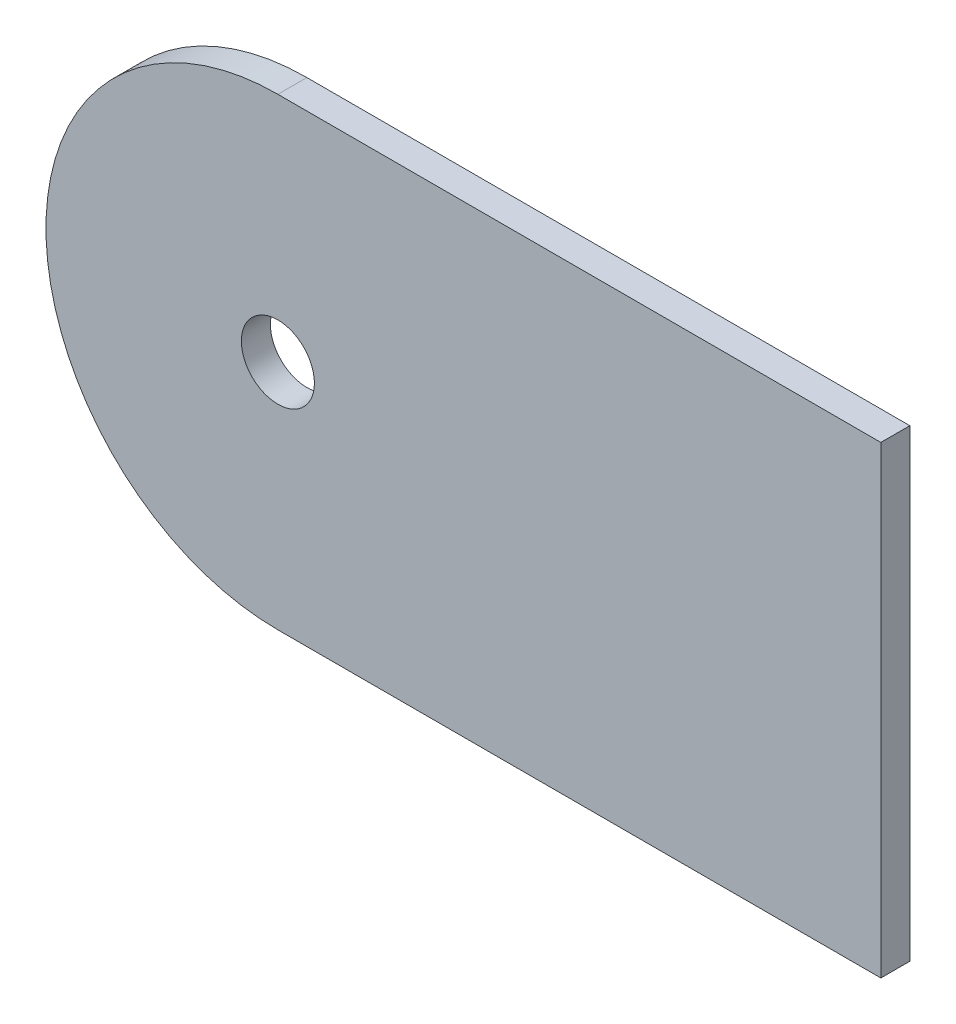
SolidWorks part; units mm, degrees
ref_plane "Front Plane" through (0, 0, 0) normal (0, 0, 1) x (1, 0, 0)
ref_plane "Top Plane" through (0, 0, 0) normal (0, 1, 0) x (1, 0, 0)
ref_plane "Right Plane" through (0, 0, 0) normal (1, 0, 0) x (0, 0, -1)
sketch "Sketch1" plane through (0, 0, 0) normal (0, 0, 1) x (1, 0, 0)
  line L1 (0, -12.7) -> (33.02, -12.7)
  line L2 (0, -12.7) -> (0, 12.7) construction
  line L3 (0, 12.7) -> (33.02, 12.7)
  line L4 (33.02, -12.7) -> (33.02, 12.7)
  arc A0 (0, 12.7) -> (0, -12.7) centre (0, 0) ccw
  circle A1 centre (0, 0) radius 2
  dimension "D3" = 4
  dimension "D1" = 25.4
  dimension "D2" = 33.02
extrude "Boss-Extrude1" add sketch "Sketch1" along normal blind 1.5875
